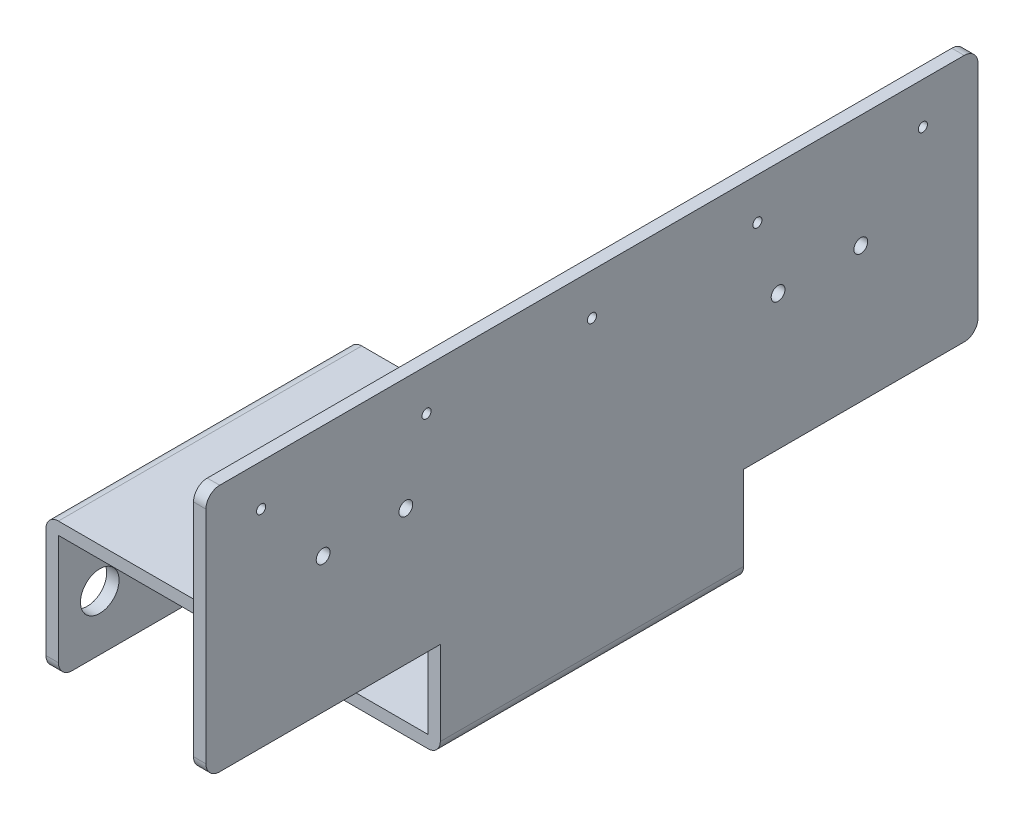
SolidWorks part; units mm, degrees
ref_plane "正面" through (0, 0, 0) normal (0, 0, 1) x (1, 0, 0)
ref_plane "平面" through (0, 0, 0) normal (0, 1, 0) x (1, 0, 0)
ref_plane "右側面" through (0, 0, 0) normal (1, 0, 0) x (0, 0, -1)
sketch "ｽｹｯﾁ1" plane through (0, 0, 0) normal (0, 0, 1) x (1, 0, 0)
  line L0 (0, 0) -> (4.5, 0)
  line L1 (4.5, 0) -> (4.5, 45)
  line L2 (4.5, 45) -> (138.5, 45)
  line L3 (143, 49.5) -> (143, 170)
  line L4 (143, 170) -> (138.5, 170)
  line L5 (138.5, 170) -> (138.5, 49.5)
  line L6 (138.5, 49.5) -> (4.5, 49.5)
  line L7 (0, 45) -> (0, 0)
  arc A0 (138.5, 45) -> (143, 49.5) centre (138.5, 49.5) ccw
  arc A1 (4.5, 49.5) -> (0, 45) centre (4.5, 45) ccw
extrude "ﾎﾞｽ - 押し出し1" add sketch "ｽｹｯﾁ1" against normal blind 55 and the other way blind 55
sketch "ｽｹｯﾁ2" plane through (0, 0, 0) normal (0, 0, 1) x (1, 0, 0)
  line L0 (138.5, 170) -> (138.5, 49.5) construction
  line L1 (138.5, 80) -> (143, 80)
  line L2 (138.5, 80) -> (138.5, 170)
  line L3 (138.5, 170) -> (143, 170)
  line L4 (143, 80) -> (143, 170)
extrude "ﾎﾞｽ - 押し出し2" add sketch "ｽｹｯﾁ2" against normal blind 140 and the other way blind 140
fillet "ﾌｨﾚｯﾄ1" radius 5 6 edges at (140.75, 80, -140) (140.75, 170, -140) (140.75, 80, 140) (140.75, 170, 140) (2.25, 0, -55) (2.25, 0, 55)
sketch "ｽｹｯﾁ3" plane through (0, 0, 0) normal (1, 0, 0) x (0, 0, -1)
  circle A0 centre (40, 20) radius 7
  circle A1 centre (-40, 20) radius 7
  circle A2 centre (0, 155) radius 1.65
  circle A3 centre (60, 155) radius 1.65
  circle A4 centre (-60, 155) radius 1.65
  circle A5 centre (120, 155) radius 1.65
  circle A6 centre (-120, 155) radius 1.65
  circle A7 centre (67.5, 129) radius 2.5
  circle A8 centre (-67.5, 129) radius 2.5
  circle A9 centre (97.5, 129) radius 2.5
  circle A10 centre (-97.5, 129) radius 2.5
extrude "ｶｯﾄ - 押し出し1" cut sketch "ｽｹｯﾁ3" against normal through all and the other way through all
